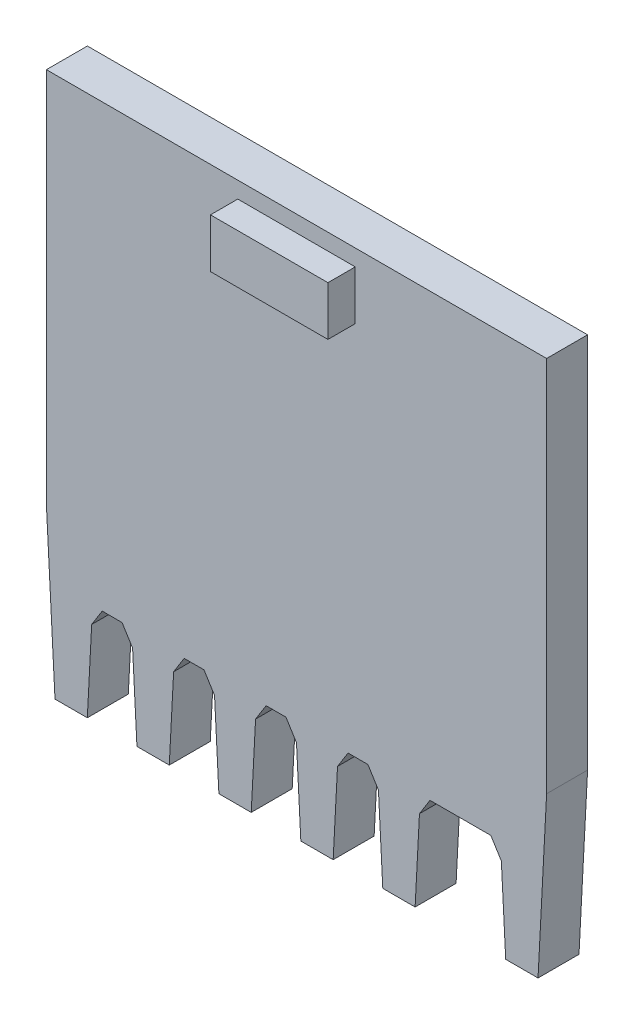
SolidWorks part; units mm, degrees
ref_plane "Front Plane" through (0, 0, 0) normal (0, 0, 1) x (1, 0, 0)
ref_plane "Top Plane" through (0, 0, 0) normal (0, 1, 0) x (1, 0, 0)
ref_plane "Right Plane" through (0, 0, 0) normal (1, 0, 0) x (0, 0, -1)
sketch "Sketch1" plane through (0, 0, 0) normal (0, 0, 1) x (1, 0, 0)
  line L0 (0, 0) -> (0, 19.8) construction
  line L1 (0, 19.8) -> (18.3124, 19.8) construction
  line L2 (18.3124, 19.8) -> (18.3124, 0) construction
  line L3 (18.3124, 0) -> (0, 0) construction
  line L4 (0, 3) -> (18.3124, 3) construction
  line L5 (0, 6) -> (18.3124, 6) construction
  line L6 (0.9062, 6) -> (0.9062, 0) construction
  line L7 (3.9062, 6) -> (3.9062, 0) construction
  line L8 (6.9062, 6) -> (6.9062, 0) construction
  line L9 (9.9062, 6) -> (9.9062, 0) construction
  line L10 (12.9062, 6) -> (12.9062, 0) construction
  line L11 (17.4062, 6) -> (17.4062, 0) construction
  line L12 (0.9062, 3) -> (3.9062, 3) construction
  line L13 (3.9062, 3) -> (6.9062, 3) construction
  line L14 (6.9062, 3) -> (9.9062, 3) construction
  line L15 (9.9062, 3) -> (12.9062, 3) construction
  line L16 (12.9062, 3) -> (17.4062, 3) construction
  line L17 (0.9062, 3) -> (0, 3) construction
  line L18 (17.4062, 3) -> (18.3124, 3) construction
  line L19 (2.4062, 3) -> (2.4062, 0) construction
  line L20 (5.4062, 3) -> (5.4062, 0) construction
  line L21 (8.4062, 3) -> (8.4062, 0) construction
  line L22 (11.4062, 3) -> (11.4062, 0) construction
  line L23 (15.1562, 3) -> (15.1562, 0) construction
  line L24 (14.4062, 3.75) -> (15.9062, 3.75) construction
  line L25 (0, 6) -> (0.3144, 0)
  line L26 (0.3144, 0) -> (1.4979, 0)
  line L27 (1.4979, 0) -> (1.6572, 3.0393)
  line L28 (3.1552, 3.0393) -> (3.3144, 0)
  line L29 (3.3144, 0) -> (4.4979, 0)
  line L30 (4.4979, 0) -> (4.6572, 3.0393)
  line L31 (6.1552, 3.0393) -> (6.3144, 0)
  line L32 (6.3144, 0) -> (7.4979, 0)
  line L33 (7.4979, 0) -> (7.6572, 3.0393)
  line L34 (9.1552, 3.0393) -> (9.3144, 0)
  line L35 (9.3144, 0) -> (10.4979, 0)
  line L36 (10.4979, 0) -> (10.6572, 3.0393)
  line L37 (12.1552, 3.0393) -> (12.3144, 0)
  line L38 (12.3144, 0) -> (13.4979, 0)
  line L39 (13.4979, 0) -> (13.6572, 3.0393)
  line L40 (16.6552, 3.0393) -> (16.8144, 0)
  line L41 (16.8144, 0) -> (17.9979, 0)
  line L42 (17.9979, 0) -> (18.3124, 6)
  line L44 (1.6572, 3.0393) -> (2.0426, 3.656)
  line L45 (0, 6) -> (0, 19.8)
  line L46 (0, 19.8) -> (18.3124, 19.8)
  line L47 (18.3124, 19.8) -> (18.3124, 6)
  line L48 (9.1562, 19.8) -> (9.1562, 6) construction
  line L49 (2.0426, 3.656) -> (2.7698, 3.656)
  line L50 (2.7698, 3.656) -> (3.1552, 3.0393)
  line L51 (4.6572, 3.0393) -> (5.0426, 3.656)
  line L52 (5.0426, 3.656) -> (5.7698, 3.656)
  line L53 (5.7698, 3.656) -> (6.1552, 3.0393)
  line L54 (7.6572, 3.0393) -> (8.0426, 3.656)
  line L55 (8.0426, 3.656) -> (8.7698, 3.656)
  line L56 (8.7698, 3.656) -> (9.1552, 3.0393)
  line L57 (10.6572, 3.0393) -> (11.0426, 3.656)
  line L58 (11.0426, 3.656) -> (11.7698, 3.656)
  line L59 (11.7698, 3.656) -> (12.1552, 3.0393)
  line L60 (13.6572, 3.0393) -> (14.0426, 3.656)
  line L61 (14.0426, 3.656) -> (16.2698, 3.656)
  line L62 (16.2698, 3.656) -> (16.6552, 3.0393)
  arc A0 (3.1552, 3.0393) -> (1.6572, 3.0393) centre (2.4062, 3) ccw construction
  arc A1 (6.1552, 3.0393) -> (4.6572, 3.0393) centre (5.4062, 3) ccw construction
  arc A2 (9.1552, 3.0393) -> (7.6572, 3.0393) centre (8.4062, 3) ccw construction
  arc A3 (12.1552, 3.0393) -> (10.6572, 3.0393) centre (11.4062, 3) ccw construction
  arc A4 (13.6572, 3.0393) -> (14.4062, 3.75) centre (14.4062, 3) cw construction
  arc A5 (16.6552, 3.0393) -> (15.9062, 3.75) centre (15.9062, 3) ccw construction
  dimension "D7" = 0.75
  dimension "D1" = 3
  dimension "D2" = 6
  dimension "D3" = 13.8
  dimension "D4" = 3
  dimension "D6" = 4.5
  dimension "D8" = 3
  dimension "D9" = 18.3124
  dimension "D10" = 19.8
extrude "Boss-Extrude1" add sketch "Sketch1" along normal blind 1.5
sketch "Sketch3" plane through (0, 0, 0) normal (0, 0, 1) x (1, 0, 0)
  line L0 (-0.4005, 6) -> (18.7129, 6)
  line L1 (18.7129, 3) -> (-0.4005, 3) construction
  line L2 (-0.4005, 0) -> (18.7129, 0) construction
  line L3 (-0.4005, -0.5) -> (18.7129, -0.5) construction
  line L4 (18.7129, -0.5) -> (18.7129, 6) construction
  line L5 (-0.4005, 6) -> (-0.4005, -0.5) construction
  line L6 (18.3124, 0) -> (0, 0) construction
  line L7 (0, 3) -> (18.3124, 3) construction
  line L8 (0, 6) -> (18.3124, 6) construction
  line L9 (0.3407, -0.5) -> (0, 6) construction
  line L10 (18.3124, 6) -> (17.9717, -0.5) construction
  line L11 (17.9979, 0) -> (18.3124, 6) construction
  line L12 (0, 6) -> (0.3144, 0) construction
  line L13 (5.4062, 6) -> (5.4062, -0.5) construction
  line L14 (3.9062, 6) -> (3.9062, -0.5) construction
  line L15 (5.4062, 3) -> (5.4062, 0) construction
  line L16 (3.1572, 3) -> (3.3407, -0.5) construction
  line L17 (2.7567, 3) -> (2.9401, -0.5)
  line L18 (3.1552, 3.0393) -> (3.3144, 0) construction
  line L19 (2.9401, -0.5) -> (4.8723, -0.5)
  line L20 (4.8723, -0.5) -> (5.0557, 3)
  line L21 (2.8484, 1.25) -> (3.2478, 1.2709) construction
  line L22 (5.9401, -0.5) -> (5.7567, 3)
  line L26 (7.8723, -0.5) -> (5.9401, -0.5)
  line L27 (8.0557, 3) -> (7.8723, -0.5)
  line L30 (2.4062, -0.5) -> (2.4062, 6) construction
  line L31 (2.4062, 3) -> (2.4062, 0) construction
  line L32 (8.4062, 6) -> (8.4062, -0.5) construction
  line L34 (11.4062, -0.5) -> (11.4062, 6) construction
  line L35 (15.1562, -0.5) -> (15.1562, 6) construction
  line L36 (8.4062, 3) -> (8.4062, 0) construction
  line L37 (11.4062, 3) -> (11.4062, 0) construction
  line L38 (15.1562, 3) -> (15.1562, 0) construction
  line L39 (10.8723, -0.5) -> (11.0557, 3)
  line L40 (8.9401, -0.5) -> (10.8723, -0.5)
  line L41 (8.7567, 3) -> (8.9401, -0.5)
  line L42 (11.9401, -0.5) -> (11.7567, 3)
  line L43 (13.8723, -0.5) -> (11.9401, -0.5)
  line L44 (14.0557, 3) -> (13.8723, -0.5)
  line L45 (16.4401, -0.5) -> (18.3723, -0.5)
  line L46 (16.2567, 3) -> (16.4401, -0.5)
  line L47 (18.3723, -0.5) -> (18.7129, 6)
  line L48 (1.8723, -0.5) -> (-0.0599, -0.5)
  line L49 (2.0557, 3) -> (1.8723, -0.5)
  line L50 (-0.0599, -0.5) -> (-0.4005, 6)
  line L51 (16.2567, 3) -> (14.0557, 3)
  line L52 (11.7567, 3) -> (11.0557, 3)
  line L53 (8.7567, 3) -> (8.0557, 3)
  line L54 (5.7567, 3) -> (5.0557, 3)
  line L55 (2.7567, 3) -> (2.0557, 3)
  dimension "D1" = 0.5
  dimension "D2" = 0.4
ref_plane "Plane1" through (3.9062, 0, 0) normal (1, 0, 0) x (0, 0, -1)
sketch "Sketch4" plane through (3.9062, 0, 0) normal (1, 0, 0) x (0, 0, -1)
  line L0 (0, 6) -> (0, -0.5) construction
  line L1 (0.6, 6) -> (-2.1, 6) construction
  line L2 (0.6, 6) -> (0.6, -0.5) construction
  line L3 (0.6, -0.5) -> (-2.1, -0.5) construction
  line L4 (-2.1, 6) -> (-2.1, -0.5) construction
  line L5 (-0.75, -0.5) -> (-0.75, 6) construction
  line L6 (-1.5, 6) -> (-1.5, -0.5) construction
  line L7 (0.6, 2.4005) -> (-2.1, 2.4005) construction
  line L8 (0.3, 6) -> (0.3, -0.5) construction
  line L9 (0.6, 2.4005) -> (3.846, 6) construction
  line L10 (2.2302, 6) -> (0.6, 4.1923) construction
  line L11 (0.6, 4.1923) -> (1.7139, 3.1878) construction
  line L12 (1.7139, 3.1878) -> (4.25, 6)
  line L13 (4.25, 6) -> (0.6, 6) construction
  line L14 (0.3, 1) -> (-1.8, 1) construction
  line L15 (-2.1, 0) -> (0.6, 0) construction
  line L16 (1.7139, 3.1878) -> (1.4912, 3.3887)
  line L17 (1.4912, 3.3887) -> (0.6, 2.4005)
  line L18 (-3.2139, 3.1878) -> (-5.75, 6)
  line L19 (-3.2139, 3.1878) -> (-2.9912, 3.3887)
  line L20 (-2.9912, 3.3887) -> (-2.1, 2.4005)
  line L21 (-2.1, 6) -> (-5.75, 6) construction
  line L22 (0.6, 3.0724) -> (3.2401, 6) construction
  arc A0 (0.4965, 2.2224) -> (0.6, -0.5) centre (4.2, 1) ccw
  arc A1 (0.6, 2.4005) -> (0.4965, 2.2224) centre (0.9713, 2.0656) ccw
  arc A2 (-2.1, 2.4005) -> (-1.9965, 2.2224) centre (-2.4713, 2.0656) cw
  arc A3 (-1.9965, 2.2224) -> (-2.1, -0.5) centre (-5.7, 1) cw
  dimension "D6" = 0.5
  dimension "D1" = 0.6
  dimension "D2" = 0.3
  dimension "D3" = 1.5
  dimension "D4" = 1
  dimension "D5" = 0.3
  dimension "D7" = 10
sketch "Sketch5" plane through (0, 0, 0) normal (1, 0, 0) x (0, 0, -1)
  line L0 (2.2302, 6) -> (0.6, 4.1923) construction
  line L1 (0.6, 4.1923) -> (1.7139, 3.1878) construction
  line L2 (1.7139, 3.1878) -> (4.25, 6) construction
  line L3 (2.2302, 6) -> (0.6, 4.1923) construction
  line L4 (0.6, 4.1923) -> (1.7139, 3.1878) construction
  line L5 (1.7139, 3.1878) -> (4.25, 6) construction
ref_plane "Plane2" through (0, 2.6105, -2.3541) normal (0, 0.7426, -0.6697) x (1, 0, 0)
sketch "Sketch6" plane through (0, 2.6105, -2.3541) normal (0, 0.7426, -0.6697) x (1, 0, 0)
  line L1 (3.9062, -2.362) -> (3.9062, -0.862) construction
  line L2 (3.9062, -2.362) -> (3.9062, -5.0612) construction
  line L3 (4.6562, -5.0612) -> (3.1562, -5.0612)
  line L4 (4.6562, -1.612) -> (3.1562, -1.612) construction
  line L5 (3.1562, -1.612) -> (3.1562, -5.0612)
  line L6 (4.6562, -1.612) -> (4.6562, -5.0612)
  line L10 (2.4062, -5.0612) -> (15.1562, -5.0612) construction
  line L11 (15.1562, -5.0612) -> (15.1562, -0.862) construction
  line L12 (15.1562, -0.862) -> (2.4062, -0.862) construction
  line L13 (2.4062, -0.862) -> (2.4062, -5.0612) construction
  line L14 (15.1562, 0.3349) -> (15.1562, -4.0182) construction
  line L15 (2.4062, 0.3349) -> (2.4062, -4.0182) construction
  line L16 (11.4062, -5.0612) -> (11.4062, -0.862) construction
  line L17 (8.4062, -5.0612) -> (8.4062, -0.862) construction
  line L18 (5.4062, -5.0612) -> (5.4062, -0.862) construction
  line L19 (5.4062, -4.0182) -> (5.4062, 0.3349) construction
  line L20 (8.4062, -4.0182) -> (8.4062, 0.3349) construction
  line L21 (11.4062, 0.3349) -> (11.4062, -4.0182) construction
  line L22 (0.1562, -1.612) -> (0.1562, -5.0612)
  line L23 (0.1562, -5.0612) -> (1.6562, -5.0612)
  line L24 (1.6562, -1.612) -> (1.6562, -5.0612)
  line L25 (7.6562, -1.612) -> (7.6562, -5.0612)
  line L26 (6.1562, -5.0612) -> (7.6562, -5.0612)
  line L27 (6.1562, -1.612) -> (6.1562, -5.0612)
  line L28 (10.6562, -1.612) -> (10.6562, -5.0612)
  line L29 (10.6562, -5.0612) -> (9.1562, -5.0612)
  line L30 (9.1562, -1.612) -> (9.1562, -5.0612)
  line L31 (13.6562, -1.612) -> (13.6562, -5.0612)
  line L32 (12.1562, -5.0612) -> (13.6562, -5.0612)
  line L33 (12.1562, -1.612) -> (12.1562, -5.0612)
  line L34 (18.1562, -1.612) -> (18.1562, -5.0612)
  line L35 (18.1562, -5.0612) -> (16.6562, -5.0612)
  line L36 (16.6562, -1.612) -> (16.6562, -5.0612)
  circle A0 centre (3.9062, -1.612) radius 0.75 construction
  arc A1 (4.6562, -1.612) -> (3.1562, -1.612) centre (3.9062, -1.612) ccw
  arc A2 (0.1562, -1.612) -> (1.6562, -1.612) centre (0.9062, -1.612) cw
  arc A3 (6.1562, -1.612) -> (7.6562, -1.612) centre (6.9062, -1.612) cw
  arc A4 (10.6562, -1.612) -> (9.1562, -1.612) centre (9.9062, -1.612) ccw
  arc A5 (12.1562, -1.612) -> (13.6562, -1.612) centre (12.9062, -1.612) cw
  arc A6 (18.1562, -1.612) -> (16.6562, -1.612) centre (17.4062, -1.612) ccw
ref_plane "Plane3" through (0, 1.6223, -1.463) normal (0, 0.7426, -0.6697) x (1, 0, 0)
sketch "Sketch7" plane through (0, 1.6223, -1.463) normal (0, 0.7426, -0.6697) x (1, 0, 0)
  line L0 (3.1562, -1.612) -> (3.1562, -5.0612) construction
  line L1 (4.6562, -5.0612) -> (3.1562, -5.0612) construction
  line L2 (4.6562, -1.612) -> (4.6562, -5.0612) construction
  line L3 (3.1562, -1.612) -> (3.1562, -5.0612) construction
  line L4 (4.6562, -5.0612) -> (3.1562, -5.0612) construction
  line L5 (4.6562, -1.612) -> (4.6562, -5.0612) construction
  line L6 (3.9062, -0.862) -> (3.9062, -5.0612) construction
  line L7 (4.6562, -1.612) -> (3.1562, -1.612) construction
  line L8 (4.6562, -2.362) -> (3.1562, -2.362) construction
  line L9 (3.4562, -1.612) -> (3.4562, -2.362)
  line L10 (3.4562, -2.362) -> (4.3562, -2.362)
  line L11 (4.3562, -2.362) -> (4.3562, -1.612)
  line L12 (2.4062, -0.862) -> (2.4062, -5.0612) construction
  line L13 (2.4062, -5.0612) -> (15.1562, -5.0612) construction
  line L14 (15.1562, -0.862) -> (2.4062, -0.862) construction
  line L15 (5.4062, -5.0612) -> (5.4062, -0.862) construction
  line L16 (8.4062, -5.0612) -> (8.4062, -0.862) construction
  line L17 (11.4062, -5.0612) -> (11.4062, -0.862) construction
  line L18 (15.1562, -5.0612) -> (15.1562, -0.862) construction
  line L19 (2.4062, -0.862) -> (2.4062, -5.0612) construction
  line L20 (2.4062, -5.0612) -> (15.1562, -5.0612) construction
  line L21 (15.1562, -0.862) -> (2.4062, -0.862) construction
  line L22 (5.4062, -5.0612) -> (5.4062, -0.862) construction
  line L23 (8.4062, -5.0612) -> (8.4062, -0.862) construction
  line L24 (11.4062, -5.0612) -> (11.4062, -0.862) construction
  line L25 (15.1562, -5.0612) -> (15.1562, -0.862) construction
  line L26 (0.4562, -2.362) -> (0.4562, -1.612)
  line L27 (1.3562, -2.362) -> (0.4562, -2.362)
  line L28 (1.3562, -1.612) -> (1.3562, -2.362)
  line L29 (7.3562, -2.362) -> (6.4562, -2.362)
  line L30 (7.3562, -1.612) -> (7.3562, -2.362)
  line L31 (6.4562, -2.362) -> (6.4562, -1.612)
  line L32 (9.4562, -1.612) -> (9.4562, -2.362)
  line L33 (10.3562, -2.362) -> (10.3562, -1.612)
  line L34 (9.4562, -2.362) -> (10.3562, -2.362)
  line L35 (13.3562, -1.612) -> (13.3562, -2.362)
  line L36 (12.4562, -2.362) -> (12.4562, -1.612)
  line L37 (13.3562, -2.362) -> (12.4562, -2.362)
  line L38 (16.9562, -1.612) -> (16.9562, -2.362)
  line L39 (17.8562, -2.362) -> (17.8562, -1.612)
  line L40 (16.9562, -2.362) -> (17.8562, -2.362)
  arc A0 (4.6562, -1.612) -> (3.1562, -1.612) centre (3.9062, -1.612) ccw construction
  arc A1 (4.6562, -1.612) -> (3.1562, -1.612) centre (3.9062, -1.612) ccw construction
  circle A2 centre (3.9062, -1.612) radius 0.45 construction
  arc A3 (4.3562, -1.612) -> (3.4562, -1.612) centre (3.9062, -1.612) ccw
  arc A4 (0.4562, -1.612) -> (1.3562, -1.612) centre (0.9062, -1.612) cw
  arc A5 (6.4562, -1.612) -> (7.3562, -1.612) centre (6.9062, -1.612) cw
  arc A6 (10.3562, -1.612) -> (9.4562, -1.612) centre (9.9062, -1.612) ccw
  arc A7 (12.4562, -1.612) -> (13.3562, -1.612) centre (12.9062, -1.612) cw
  arc A8 (17.8562, -1.612) -> (16.9562, -1.612) centre (17.4062, -1.612) ccw
ref_plane "bisect" through (0, 0, 0.75) normal (0, 0, 1) x (1, 0, 0)
ref_plane "insert_surface" through (0, 6, 0) normal (0, 1, 0) x (1, 0, 0)
sketch "Sketch8" plane through (0, 6, 0) normal (0, 1, 0) x (1, 0, 0)
  line L0 (18.7129, -0.75) -> (-0.4005, -0.75) construction
  line L1 (-0.4005, 0.6) -> (18.7129, 0.6)
  line L2 (-0.4005, 0.6) -> (-0.4005, -2.1)
  line L3 (-0.4005, -2.1) -> (18.7129, -2.1)
  line L4 (18.7129, 0.6) -> (18.7129, -2.1)
  line L5 (9.1562, 0.6) -> (9.1562, -2.1) construction
  line L6 (0, 0) -> (18.3124, 0) construction
  line L7 (0, 0) -> (0, -1.5) construction
  line L8 (0, -1.5) -> (18.3124, -1.5) construction
  line L9 (18.3124, 0) -> (18.3124, -1.5) construction
  line L10 (18.7129, 0.3) -> (-0.4005, 0.3) construction
  line L11 (18.7129, -1.8) -> (-0.4005, -1.8) construction
sketch "Sketch9" plane through (0, 0, 0) normal (0, 0, 1) x (1, 0, 0)
  line L0 (18.3723, -0.5) -> (18.7129, 6) construction
  line L1 (-0.4005, 6) -> (18.7129, 6) construction
  line L2 (-0.0599, -0.5) -> (-0.4005, 6) construction
  line L3 (1.8723, -0.5) -> (-0.0599, -0.5) construction
  line L4 (2.0557, 3) -> (1.8723, -0.5) construction
  line L5 (2.7567, 3) -> (2.0557, 3) construction
  line L6 (2.7567, 3) -> (2.9401, -0.5) construction
  line L7 (2.9401, -0.5) -> (4.8723, -0.5) construction
  line L8 (4.8723, -0.5) -> (5.0557, 3) construction
  line L9 (5.7567, 3) -> (5.0557, 3) construction
  line L10 (5.9401, -0.5) -> (5.7567, 3) construction
  line L11 (7.8723, -0.5) -> (5.9401, -0.5) construction
  line L12 (8.0557, 3) -> (7.8723, -0.5) construction
  line L13 (8.7567, 3) -> (8.0557, 3) construction
  line L14 (8.7567, 3) -> (8.9401, -0.5) construction
  line L15 (8.9401, -0.5) -> (10.8723, -0.5) construction
  line L16 (10.8723, -0.5) -> (11.0557, 3) construction
  line L17 (11.7567, 3) -> (11.0557, 3) construction
  line L18 (11.9401, -0.5) -> (11.7567, 3) construction
  line L19 (13.8723, -0.5) -> (11.9401, -0.5) construction
  line L20 (14.0557, 3) -> (13.8723, -0.5) construction
  line L21 (16.2567, 3) -> (14.0557, 3) construction
  line L22 (16.2567, 3) -> (16.4401, -0.5) construction
  line L23 (16.4401, -0.5) -> (18.3723, -0.5) construction
  line L24 (18.3723, -0.5) -> (18.7129, 6)
  line L25 (-0.4005, 6) -> (18.7129, 6) construction
  line L26 (-0.0599, -0.5) -> (-0.4005, 6)
  line L27 (1.8723, -0.5) -> (-0.0599, -0.5)
  line L28 (2.0557, 3) -> (1.8723, -0.5)
  line L29 (2.7567, 3) -> (2.0557, 3) construction
  line L30 (2.7567, 3) -> (2.9401, -0.5)
  line L31 (2.9401, -0.5) -> (4.8723, -0.5)
  line L32 (4.8723, -0.5) -> (5.0557, 3)
  line L33 (5.7567, 3) -> (5.0557, 3) construction
  line L34 (5.9401, -0.5) -> (5.7567, 3)
  line L35 (7.8723, -0.5) -> (5.9401, -0.5)
  line L36 (8.0557, 3) -> (7.8723, -0.5)
  line L37 (8.7567, 3) -> (8.0557, 3) construction
  line L38 (8.7567, 3) -> (8.9401, -0.5)
  line L39 (8.9401, -0.5) -> (10.8723, -0.5)
  line L40 (10.8723, -0.5) -> (11.0557, 3)
  line L41 (11.7567, 3) -> (11.0557, 3) construction
  line L42 (11.9401, -0.5) -> (11.7567, 3)
  line L43 (13.8723, -0.5) -> (11.9401, -0.5)
  line L44 (14.0557, 3) -> (13.8723, -0.5)
  line L45 (16.2567, 3) -> (14.0557, 3) construction
  line L46 (16.2567, 3) -> (16.4401, -0.5)
  line L47 (16.4401, -0.5) -> (18.3723, -0.5)
  line L48 (16.2567, 3) -> (16.2567, 6)
  line L49 (14.0557, 3) -> (14.0557, 6)
  line L50 (11.7567, 3) -> (11.7567, 6)
  line L51 (18.7129, 6) -> (-0.4005, 6) construction
  line L52 (11.0557, 3) -> (11.0557, 6)
  line L53 (-0.4005, 6) -> (18.7129, 6) construction
  line L54 (8.7567, 3) -> (8.7567, 6)
  line L55 (8.0557, 3) -> (8.0557, 6)
  line L58 (5.7567, 3) -> (5.7567, 6)
  line L60 (5.0557, 3) -> (5.0557, 6)
  line L62 (15.1562, -0.5) -> (15.1562, 6) construction
  line L63 (15.1562, -0.5) -> (15.1562, 6) construction
  line L64 (2.7567, 3) -> (2.7567, 6)
  line L65 (2.0557, 3) -> (2.0557, 6)
  line L67 (18.7129, 6) -> (16.2567, 6)
  line L68 (14.0557, 6) -> (11.7567, 6)
  line L69 (11.0557, 6) -> (8.7567, 6)
  line L70 (8.0557, 6) -> (5.7567, 6)
  line L71 (5.0557, 6) -> (2.7567, 6)
  line L72 (2.0557, 6) -> (-0.4005, 6)
sketch "rgb_led" plane through (0, 0, 1.5) normal (0, 0, 1) x (1, 0, 0)
  line L0 (18.3124, 16.8) -> (0, 16.8) construction
  line L1 (18.3124, 6) -> (18.3124, 19.8) construction
  line L2 (0, 19.8) -> (0, 6) construction
  line L3 (9.1562, 19.8) -> (9.1562, 16.8) construction
  line L4 (18.3124, 19.8) -> (0, 19.8) construction
  line L6 (12.0562, 18.6) -> (6.2562, 18.6)
  line L7 (12.0562, 18.6) -> (12.0562, 15)
  line L8 (12.0562, 15) -> (6.2562, 15)
  line L9 (6.2562, 18.6) -> (6.2562, 15)
  dimension "D1" = 3
  dimension "D2" = 3.6
  dimension "D3" = 5.8
sketch "Sketch11" plane through (0, 0, 0) normal (0, 0, 1) x (1, 0, 0)
  line L0 (18.3124, 19.8) -> (18.3124, 6) construction
  line L1 (11.3062, 19.2) -> (7.0062, 19.2)
  line L2 (11.3062, 19.2) -> (11.3062, 17.4)
  line L3 (11.3062, 17.4) -> (7.0062, 17.4)
  line L4 (7.0062, 19.2) -> (7.0062, 17.4)
  line L5 (18.3124, 6) -> (0, 6) construction
  line L6 (0, 6) -> (0, 19.8) construction
  line L7 (0, 19.8) -> (18.3124, 19.8) construction
  line L8 (9.1562, 17.4) -> (9.1562, 6) construction
  line L9 (9.1562, 19.2) -> (9.1562, 17.4) construction
  line L10 (11.3062, 18.3) -> (9.1562, 18.3) construction
  line L11 (7.0062, 18.3) -> (9.1562, 18.3) construction
  dimension "D1" = 7.0062
  dimension "D2" = 11.4
  dimension "D3" = 1.8
  dimension "D4" = 4.3
extrude "Boss-Extrude3" add sketch "Sketch11" along normal blind 1 from surface starting at face at (8.6562, 3.2931, 1.5)
ref_axis "Axis1" through (9.1562, 18.3, 2.629) along (0, 0, 1)
ref_plane "right_center" through (9.1562, 0, 0) normal (1, 0, 0) x (0, 0, -1)
